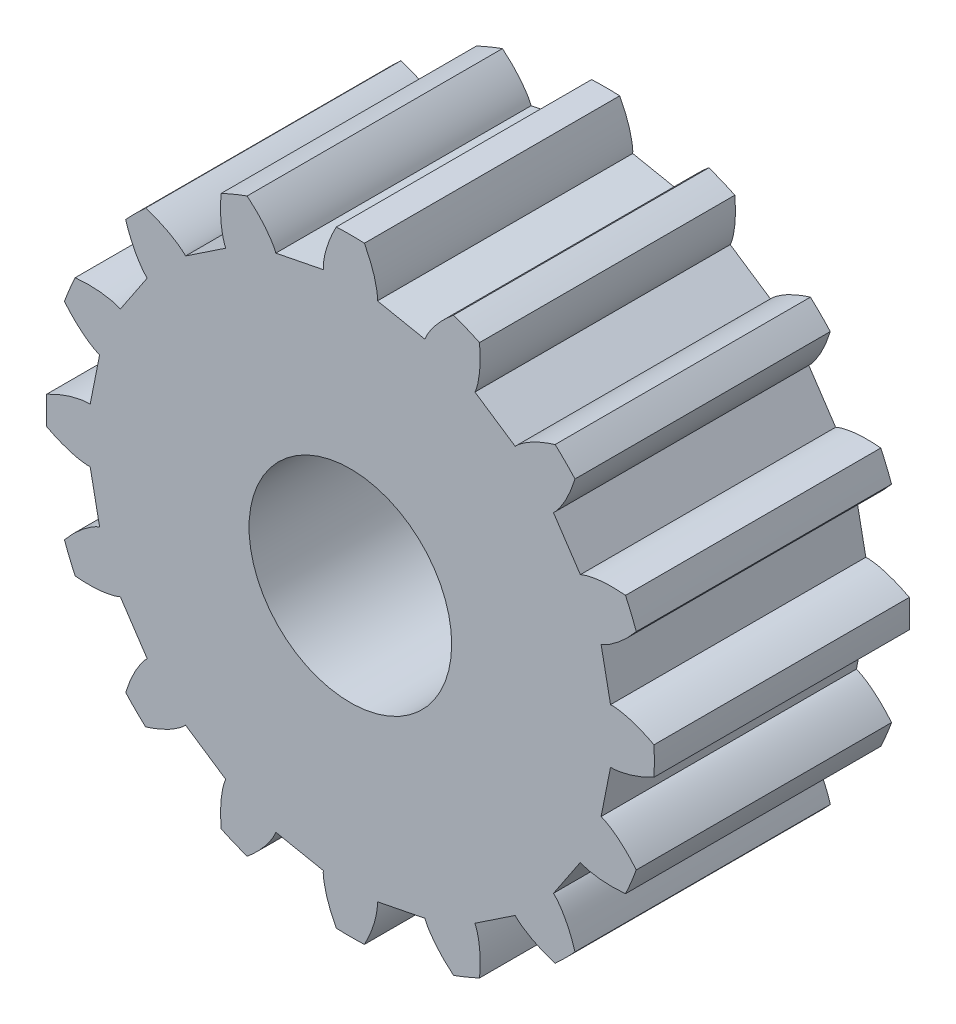
SolidWorks part; units mm, degrees
material "Plain Carbon Steel"
ref_plane "Front Plane" through (0, 0, 0) normal (0, 0, 1) x (1, 0, 0)
ref_plane "Top Plane" through (0, 0, 0) normal (0, 1, 0) x (1, 0, 0)
ref_plane "Right Plane" through (0, 0, 0) normal (1, 0, 0) x (0, 0, -1)
sketch "Sketch1" plane through (0, 0, 0) normal (0, 0, 1) x (1, 0, 0)
  circle A0 centre (0, 0) radius 14.2875
  dimension "D1" = 28.575
extrude "Boss-Extrude1" add sketch "Sketch1" along normal blind 12
sketch "Sketch2" plane through (0, 0, 0) normal (0, 0, 1) x (1, 0, 0)
  spline S0 degree 4 poles (12.2294, 1.273) (12.2326, 1.2733) (12.2415, 1.274) (12.2584, 1.2748) (12.286, 1.2754) (12.3212, 1.2753) (12.3668, 1.2738) (12.4205, 1.2707) (12.4797, 1.2656) (12.5441, 1.2584) (12.6083, 1.2497) (12.6724, 1.2397) (12.7362, 1.2284) (12.8134, 1.2132) (12.906, 1.193) (13.014, 1.1663) (13.1364, 1.1326) (13.2609, 1.0943) (13.3831, 1.0536) (13.5062, 1.0089) (13.6252, 0.9632) (13.7483, 0.912) (13.8617, 0.8629) (13.9883, 0.8039) (14.0903, 0.7551) (14.2242, 0.6865) (14.3032, 0.6448) (14.3953, 0.5944) (14.4361, 0.5713) (14.4612, 0.5571) knots 0 0 0 0 0 0.005377 0.015084 0.028532 0.04661 0.064855 0.092111 0.119476 0.146842 0.174209 0.201575 0.228941 0.256307 0.307035 0.361767 0.4165 0.471232 0.525964 0.580697 0.635429 0.690161 0.744894 0.799626 0.854358 0.909091 0.954545 1 1 1 1 1 construction
  spline S1 degree 4 poles (12.2294, 1.273) (12.2326, 1.2733) (12.2415, 1.274) (12.2584, 1.2748) (12.286, 1.2754) (12.3212, 1.2753) (12.3668, 1.2738) (12.4205, 1.2707) (12.4797, 1.2656) (12.5441, 1.2584) (12.6083, 1.2497) (12.6724, 1.2397) (12.7362, 1.2284) (12.8134, 1.2132) (12.906, 1.193) (13.014, 1.1663) (13.1364, 1.1326) (13.2609, 1.0943) (13.3831, 1.0536) (13.5062, 1.0089) (13.6252, 0.9632) (13.7483, 0.912) (13.8617, 0.8629) (13.9883, 0.8039) (14.0903, 0.7551) (14.1952, 0.7014) (14.2462, 0.6748) (14.2722, 0.661) knots 0 0 0 0 0 0.005377 0.015084 0.028532 0.04661 0.064855 0.092111 0.119476 0.146842 0.174209 0.201575 0.228941 0.256307 0.307035 0.361767 0.4165 0.471232 0.525964 0.580697 0.635429 0.690161 0.744894 0.799626 0.854358 0.909091 0.909091 0.909091 0.909091 0.909091
  spline S2 degree 4 poles (11.7856, 3.5039) (11.7887, 3.5048) (11.7972, 3.5076) (11.8131, 3.5133) (11.8388, 3.5233) (11.8713, 3.5369) (11.9129, 3.5557) (11.9614, 3.5792) (12.0141, 3.6065) (12.0708, 3.6378) (12.1268, 3.6704) (12.1821, 3.7042) (12.2368, 3.739) (12.3023, 3.7826) (12.3801, 3.8367) (12.4697, 3.9027) (12.5699, 3.9807) (12.6702, 4.0637) (12.7676, 4.1481) (12.8642, 4.2365) (12.9566, 4.3243) (13.0508, 4.4187) (13.1368, 4.5074) (13.2311, 4.6104) (13.3067, 4.6945) (13.4042, 4.8091) (13.4611, 4.8779) (13.527, 4.9597) (13.5558, 4.9967) (13.5736, 5.0194) knots 0 0 0 0 0 0.005377 0.015084 0.028532 0.04661 0.064855 0.092111 0.119476 0.146842 0.174209 0.201575 0.228941 0.256307 0.307035 0.361767 0.4165 0.471232 0.525964 0.580697 0.635429 0.690161 0.744894 0.799626 0.854358 0.909091 0.954545 1 1 1 1 1 construction
  spline S3 degree 4 poles (11.7856, 3.5039) (11.7887, 3.5048) (11.7972, 3.5076) (11.8131, 3.5133) (11.8388, 3.5233) (11.8713, 3.5369) (11.9129, 3.5557) (11.9614, 3.5792) (12.0141, 3.6065) (12.0708, 3.6378) (12.1268, 3.6704) (12.1821, 3.7042) (12.2368, 3.739) (12.3023, 3.7826) (12.3801, 3.8367) (12.4697, 3.9027) (12.5699, 3.9807) (12.6702, 4.0637) (12.7676, 4.1481) (12.8642, 4.2365) (12.9566, 4.3243) (13.0508, 4.4187) (13.1368, 4.5074) (13.2311, 4.6104) (13.3067, 4.6945) (13.3831, 4.7842) (13.42, 4.8284) (13.4387, 4.8511) knots 0 0 0 0 0 0.005377 0.015084 0.028532 0.04661 0.064855 0.092111 0.119476 0.146842 0.174209 0.201575 0.228941 0.256307 0.307035 0.361767 0.4165 0.471232 0.525964 0.580697 0.635429 0.690161 0.744894 0.799626 0.854358 0.909091 0.909091 0.909091 0.909091 0.909091
  spline S4 degree 1 poles (11.7856, 3.5039) (12.2294, 1.273) knots 0 0 1 1 construction
  spline S5 degree 1 poles (11.7856, 3.5039) (12.2294, 1.273) knots 0 0 1 1
  spline S6 degree 1 poles (14.2722, 0.661) (59.9358, 2.7757) knots 0 0 1 1 construction
  spline S7 degree 1 poles (14.2722, 0.661) (59.9358, 2.7757) knots 0 0 1 1
  spline S8 degree 4 poles (59.9924, 0.9679) (59.9914, 1.0088) (59.9898, 1.0795) (59.9907, 1.1275) (59.9804, 1.476) (59.9801, 1.6756) (59.9479, 2.5069) (59.9368, 2.7775) (59.9022, 3.4404) (59.8776, 3.8389) (59.8408, 4.3845) (59.7915, 5.0197) (59.7245, 5.7708) (59.636, 6.6216) (59.5352, 7.4745) (59.4224, 8.3239) (59.2973, 9.1728) (59.1602, 10.019) (59.0109, 10.8638) (58.8497, 11.7057) (58.6762, 12.5461) (58.4912, 13.3827) (58.2935, 14.2185) (58.085, 15.0482) (57.8629, 15.88) (57.632, 16.7001) (57.3841, 17.531) (57.1335, 18.3336) (56.8891, 19.0737) (56.6979, 19.635) (56.4391, 20.3656) (56.342, 20.6304) (56.0571, 21.4012) (55.9787, 21.592) (55.8562, 21.9145) (55.8362, 21.9603) (55.8108, 22.0259) (55.7963, 22.0637) knots 0 0 0 0 0 0.00524 0.010479 0.020959 0.041918 0.083333 0.103175 0.123016 0.142857 0.162698 0.202381 0.242063 0.281746 0.321429 0.361111 0.400794 0.440476 0.480159 0.519841 0.559524 0.599206 0.638889 0.678571 0.718254 0.757937 0.797619 0.837302 0.876984 0.896825 0.916667 0.958082 0.979041 0.989521 0.99476 1 1 1 1 1 construction
  spline S9 degree 4 poles (59.9358, 2.7757) (59.9316, 2.8649) (59.9226, 3.0495) (59.9022, 3.4404) (59.8776, 3.8389) (59.8408, 4.3845) (59.7915, 5.0197) (59.7245, 5.7708) (59.636, 6.6216) (59.5352, 7.4745) (59.4224, 8.3239) (59.2973, 9.1728) (59.1602, 10.019) (59.0109, 10.8638) (58.8497, 11.7057) (58.6762, 12.5461) (58.4912, 13.3827) (58.2935, 14.2185) (58.085, 15.0482) (57.8629, 15.88) (57.632, 16.7001) (57.3841, 17.531) (57.1335, 18.3336) (56.8891, 19.0737) (56.6979, 19.635) (56.5279, 20.115) (56.466, 20.288) (56.4356, 20.372) knots 0.083333 0.083333 0.083333 0.083333 0.083333 0.103175 0.123016 0.142857 0.162698 0.202381 0.242063 0.281746 0.321429 0.361111 0.400794 0.440476 0.480159 0.519841 0.559524 0.599206 0.638889 0.678571 0.718254 0.757937 0.797619 0.837302 0.876984 0.896825 0.916667 0.916667 0.916667 0.916667 0.916667
  spline S10 degree 1 poles (56.4356, 20.372) (13.4387, 4.8511) knots 0 0 1 1 construction
  spline S11 degree 1 poles (56.4356, 20.372) (13.4387, 4.8511) knots 0 0 1 1
extrude "Cut-Extrude2" cut sketch "Sketch2" against normal blind 13 and the other way blind 13
ref_axis "Axis1" through (0, 0, -0.6) along (0, 0, 1)
pattern_circular "CirPattern1" count 16 over 360 about axis through (0, 0, -0.6) along (0, 0, 1) of "Cut-Extrude2"
sketch "Sketch3" plane through (0, 0, 0) normal (0, 0, 1) x (1, 0, 0)
  circle A0 centre (0, 0) radius 4.7625
  dimension "D1" = 9.525
extrude "Cut-Extrude4" cut sketch "Sketch3" against normal blind 14 and the other way blind 14
ref_axis "Axis2" through (0, 0, -0.6) along (0, 0, 1)
